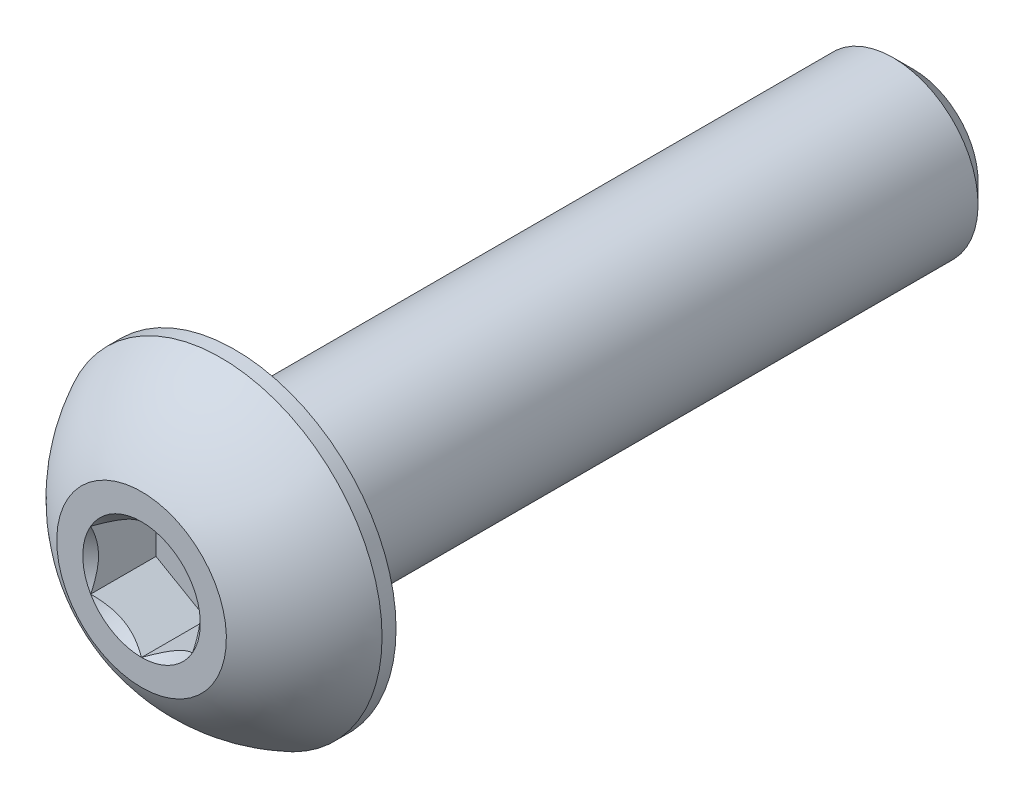
SolidWorks part; units mm, degrees
ref_plane "Front" through (0, 0, 0) normal (0, 0, 1) x (1, 0, 0)
ref_plane "Top" through (0, 0, 0) normal (0, 1, 0) x (1, 0, 0)
ref_plane "Right" through (0, 0, 0) normal (1, 0, 0) x (0, 0, -1)
sketch "Sketch1" plane through (0, 0, 0) normal (1, 0, 0) x (0, 0, -1)
  line L2 (2.75, 2.5) -> (22.75, 2.5)
  line L3 (22.75, 2.5) -> (22.75, 0)
  line L4 (22.75, 0) -> (2.75, 0)
  line L6 (2.3375, 4.75) -> (2.75, 4.75) construction
  line L7 (22.75, 2.5) -> (22.75, -2.5) construction
  line L8 (0, 0) -> (2.75, 0) construction
  line L9 (2.75, 4.75) -> (2.75, -4.75) construction
  line L11 (2.75, 2.5) -> (2.75, 0)
  line L13 (0, 1.5) -> (0, -1.5) construction
  line L14 (0, 1.5) -> (0, 2.5) construction
  arc A3 (0, 2.5) -> (2.3375, 4.75) centre (4.6581, 0) cw construction
  dimension "D1" = 0.4125
revolve "Revolve1" add sketch "Sketch1" angle 360 mid plane about L4
sketch "Sketch3" plane through (0, 0, -22.75) normal (0, 0, -1) x (-1, 0, 0)
  circle A0 centre (0, 0) radius 2.5
curve "Helix/Spiral1" pitch 0.8 height 20.8 turns 26
chamfer "Chamfer1" distance 0.6 angle 45 1 edges at (0, 2.5, -22.75)
sketch "Sketch7" plane through (0, 0, 0) normal (1, 0, 0) x (0, 0, -1)
  line L6 (2.3375, 4.75) -> (2.75, 4.75) construction
  line L8 (0, 0) -> (2.75, 0) construction
  line L11 (2.75, 4.75) -> (2.75, -4.75) construction
  line L12 (2.3375, 4.75) -> (2.75, 4.75)
  line L13 (0, 0) -> (2.75, 0)
  line L14 (0, 1.5) -> (0, -1.5) construction
  line L15 (2.75, 4.75) -> (2.75, 0)
  line L16 (0, 2.5) -> (0, 0)
  arc A2 (2.3375, 4.75) -> (0, 2.5) centre (4.6581, 0) ccw construction
  arc A3 (2.3375, 4.75) -> (0, 2.5) centre (4.6581, 0) ccw
revolve "Revolve2" add sketch "Sketch7" angle 360 mid plane about L13
sketch "Sketch5" plane through (0, 0, 0) normal (0, 0, 1) x (1, 0, 0)
  line L1 (1.5, -0.866) -> (1.5, 0.866)
  line L2 (1.5, 0.866) -> (0, 1.7321)
  line L3 (0, 1.7321) -> (-1.5, 0.866)
  line L4 (-1.5, 0.866) -> (-1.5, -0.866)
  line L5 (-1.5, -0.866) -> (0, -1.7321)
  line L6 (0, -1.7321) -> (1.5, -0.866)
  circle A0 centre (0, 0) radius 1.5 construction
extrude "Cut-Extrude2" cut sketch "Sketch5" against normal blind 1.925
sketch "Sketch6" plane through (0, 0, 0) normal (0, 0, 1) x (1, 0, 0)
  circle A0 centre (0, 0) radius 1.7321
extrude "Cut-Extrude3" cut sketch "Sketch6" against normal blind 1.925 draft 45
sketch "Sketch2" plane through (0, 0, 0) normal (1, 0, 0) x (0, 0, -1)
  line L0 (22.15, 2.5) -> (22.85, 2.5)
  line L1 (22.85, 2.5) -> (22.55, 1.9804)
  line L2 (22.55, 1.9804) -> (22.45, 1.9804)
  line L3 (22.45, 1.9804) -> (22.15, 2.5)
  line L4 (22.3, 2.2402) -> (22.7, 2.2402) construction
  dimension "D1" = 60
  dimension "D2" = 0.1
  dimension "D3" = 0.4
sweep "Cut-Sweep1" [suppressed] cut profiles "Sketch2" path "Helix/Spiral1"
sketch "Sketch10" plane through (0, 0, 0) normal (1, 0, 0) x (0, 0, -1)
  line L0 (22.75, 2.5) -> (22.75, -2.5) construction
  point P0 (21.55, -2.5)
  dimension "D1" = 1.2
ref_axis "Center Axis 1" through (0, 0, -8.1113) along (0, 0, 1)
ref_plane "Contact Plane 1" through (0, 0, -2.75) normal (0, 0, -1) x (-1, 0, 0)
ref_plane "Contact Plane 2" through (0, 0, 0) normal (0, 0, 1) x (1, 0, 0)
equation "\"D3@Helix/Spiral1\" = \"Lg@Sketch1\" + \"D4@Helix/Spiral1\""
equation "\"D2@Sketch2\" = \"D4@Helix/Spiral1\" * .125"
equation "\"D3@Sketch2\" = \"D4@Helix/Spiral1\" * .5"
equation "\"D1@Chamfer1\" = \"D4@Helix/Spiral1\" * .75"
equation "\"D1@Cut-Extrude2\" = \"Head Ht@Sketch1\" * .7"
equation "\"D1@Sketch1\" = \"Head Ht@Sketch1\" * .15"
equation "\"D1@Sketch10\" = \"D4@Helix/Spiral1\" * 1.5"
equation "\"D1@Cut-Extrude3\" = \"D1@Cut-Extrude2\""
